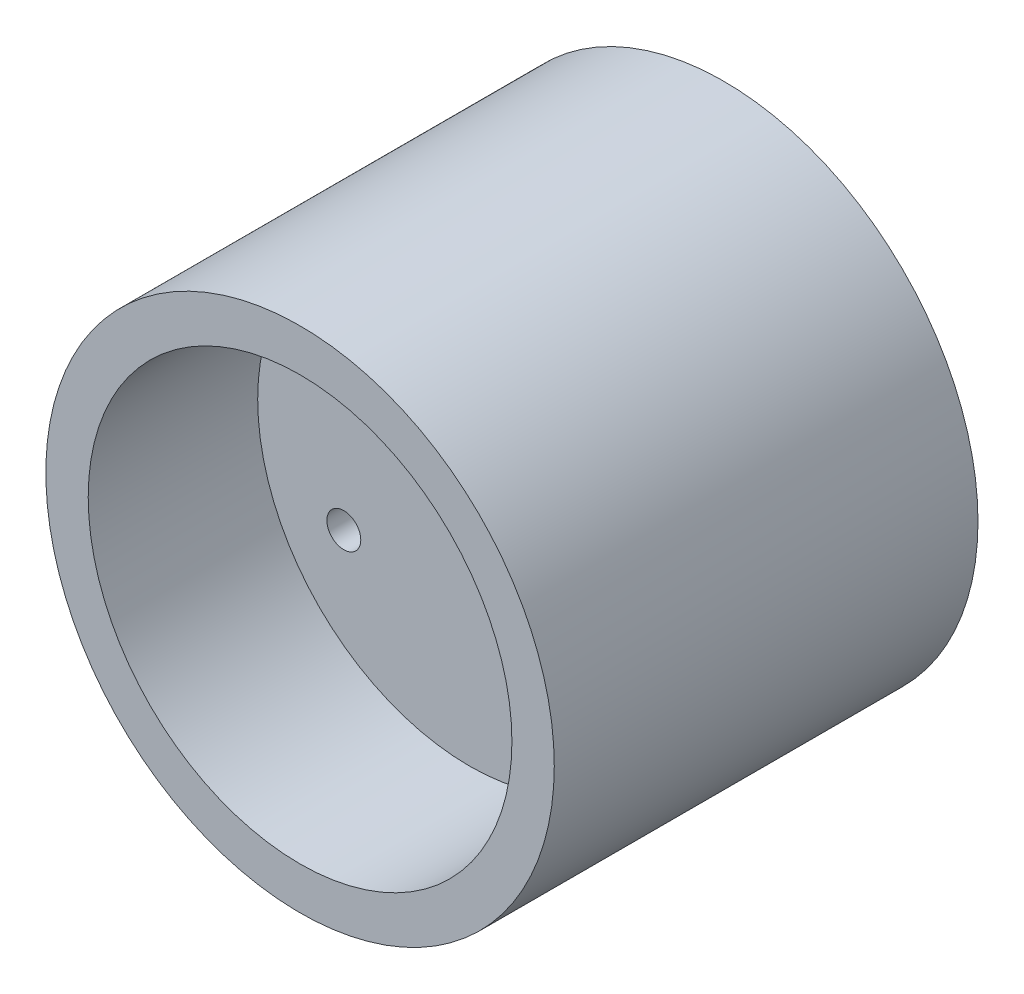
SolidWorks part; units mm, degrees
ref_plane "Ön Düzlem" through (0, 0, 0) normal (0, 0, 1) x (1, 0, 0)
ref_plane "Üst Düzlem" through (0, 0, 0) normal (0, 1, 0) x (1, 0, 0)
ref_plane "Sağ Düzlem" through (0, 0, 0) normal (1, 0, 0) x (0, 0, -1)
sketch "Çizim1" plane through (0, 0, 0) normal (0, 0, 1) x (1, 0, 0)
  circle A0 centre (-8.1488, -1.5541) radius 30
  dimension "D1" = 60
extrude "Yükseklik-Ekstrüzyon1" add sketch "Çizim1" along normal blind 50
ref_axis "Eksen1" through (-8.1488, -1.5541, 50) along (0, 0, -1)
scale "Scale1" bodies to scale 111 scale about centroid uniform scaling yes scale factor 0.5
sketch "Sketch2" plane through (0, 0, 12.5) normal (0, 0, -1) x (-1, 0, 0)
  circle A0 centre (8.1488, -1.5541) radius 12.5
  dimension "D1" = 25
extrude "Cut-Extrude1" cut sketch "Sketch2" against normal blind 5
sketch "Sketch3" plane through (0, 0, 37.5) normal (0, 0, 1) x (1, 0, 0)
  circle A0 centre (-8.1488, -1.5541) radius 12.5
  dimension "D1" = 25
extrude "Cut-Extrude2" cut sketch "Sketch3" against normal blind 10
sketch "Sketch4" plane through (0, 0, 17.5) normal (0, 0, -1) x (-1, 0, 0)
  circle A0 centre (15.5665, -5.7062) radius 1 construction
  circle A1 centre (0.8441, -5.902) radius 1 construction
  circle A2 centre (8.0358, 6.9459) radius 1 construction
  circle A3 centre (15.5665, -5.7062) radius 1
  circle A4 centre (0.8441, -5.902) radius 1
  circle A5 centre (8.0358, 6.9459) radius 1
extrude "Cut-Extrude3" cut sketch "Sketch4" against normal up to surface (10 mm away) up to face at (4.3512, -1.5541, 27.5)
